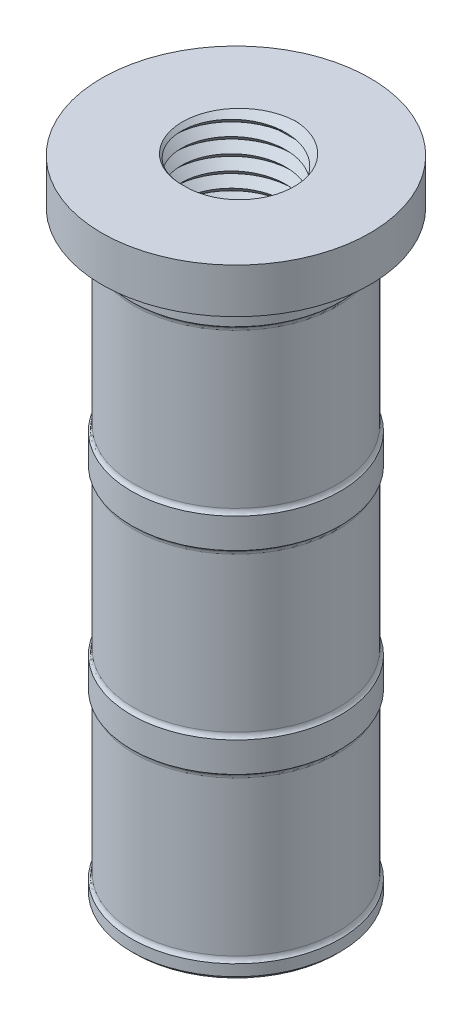
SolidWorks part; units mm, degrees
material "6061-T6 (SS)"
ref_plane "Front Plane" through (0, 0, 0) normal (0, 0, 1) x (1, 0, 0)
ref_plane "Top Plane" through (0, 0, 0) normal (0, 1, 0) x (1, 0, 0)
ref_plane "Right Plane" through (0, 0, 0) normal (1, 0, 0) x (0, 0, -1)
sketch "Sketch1" plane through (0, 0, 0) normal (1, 0, 0) x (0, 0, -1)
  line L0 (0, 48.6222) -> (0, -44.1778) construction
  line L1 (-7, 20.5) -> (-7, 18.5)
  line L2 (-6.825, -18.5) -> (-7, -18.5)
  line L3 (-7, 20.5) -> (-9, 20.5)
  line L4 (-9, 23.5) -> (-4, 23.5)
  line L5 (4.95, 0) -> (-4.95, 0) construction
  line L6 (-7, -18.5) -> (-7, -19.5)
  line L7 (-9, 23.5) -> (-9, 20.5)
  line L8 (-7, 18.5) -> (-6.825, 18.5)
  line L9 (-6.825, 18.5) -> (-6.825, 7.5)
  line L10 (-7, -19.5) -> (-4, -19.5)
  line L11 (-4, -19.5) -> (-4, 23.5)
  line L12 (-6.825, 7.5) -> (-7, 7.5)
  line L13 (-7, 7.5) -> (-7, 5.5)
  line L14 (-7, 5.5) -> (-6.825, 5.5)
  line L15 (-6.825, 5.5) -> (-6.825, -5.5)
  line L16 (-6.825, -5.5) -> (-7, -5.5)
  line L17 (-7, -5.5) -> (-7, -7.5)
  line L18 (-7, -7.5) -> (-6.825, -7.5)
  line L19 (-6.825, -7.5) -> (-6.825, -18.5)
  point P11 (-7, 19.5)
  dimension "D1" = 1
  dimension "D2" = 11
  dimension "D3" = 3
  dimension "D4" = 2
  dimension "D5" = 2
  dimension "D6" = 4
  dimension "D7" = 7
  dimension "D8" = 11
  dimension "D9" = 23.5
  dimension "D10" = 5
  dimension "D11" = 2
  dimension "D12" = 11
  dimension "D13" = 7
  dimension "D14" = 6.825
  dimension "D15" = 7
  dimension "D16" = 7
  dimension "D17" = 6.825
  dimension "D18" = 6.825
revolve "Revolve2" add sketch "Sketch1" angle 360 about L0
sketch "Sketch2" plane through (0, 0, 0) normal (1, 0, 0) x (0, 0, -1)
  line L0 (-4.0008, 23.5) -> (-4.0008, 24)
  line L3 (-4.0008, 24) -> (-3.5008, 23.5)
  line L4 (-3.5008, 23.5) -> (-4.0008, 23)
  line L5 (-4.0008, 23) -> (-4.0008, 23.5)
  line L6 (9.9, 0) -> (-9.9, 0) construction
  dimension "D1" = 0.5
  dimension "D2" = 0.5
  dimension "D3" = 0.5
  dimension "D4" = 24
ref_plane "Plane1" through (0, 23.5, 0) normal (0, 1, 0) x (1, 0, 0)
sketch "Sketch3" plane through (0, 23.5, 0) normal (0, 1, 0) x (1, 0, 0)
  circle A0 centre (0, 0) radius 4
curve "Helix/Spiral1" pitch 1 height 29 radius 4 centre (0, 23.5, 0) axis (0, -1, 0) start towards (0, 0, -1)
sweep "Sweep1" add profiles "Sketch2" path "Helix/Spiral1"
sketch "Sketch4" plane through (0, 0, 0) normal (0, 0, 1) x (1, 0, 0)
  line L0 (9, 23.5) -> (-9, 23.5) construction
  line L1 (-7.2679, 23.5) -> (7.699, 23.5)
  line L2 (-7.2679, 23.5) -> (-7.2679, 24.6372)
  line L3 (-7.2679, 24.6372) -> (7.699, 24.6372)
  line L4 (7.699, 23.5) -> (7.699, 24.6372)
  dimension "D1" = 0
extrude "Cut-Extrude1" cut sketch "Sketch4" against normal through all both and the other way through all
chamfer "Chamfer1" distance 0.25 angle 45 1 edges at (0, -19.5, 7)
sketch "Sketch6" plane through (0, 0, 0) normal (0, 0, 1) x (1, 0, 0)
  line L0 (0, 26.1079) -> (0, 11.6967) construction
  line L1 (0, -9.9) -> (0, 9.9) construction
sketch "Sketch8" plane through (0, -19.5, 0) normal (0, -1, 0) x (1, 0, 0)
  circle A0 centre (0, 0) radius 5
  dimension "D1" = 10
extrude "Cut-Extrude3" cut sketch "Sketch8" against normal blind 15
fillet "Fillet11" radius 1 1 edges at (0, -4.5, -5)
fillet "Fillet12" radius 0.4 6 edges at (0, -7.5, 6.825) (0, -18.5, 6.825) (0, 5.5, 6.825) (0, -5.5, 6.825) (0, 18.5, 6.825) (0, 7.5, 6.825)
fillet "Fillet13" radius 0.5 1 edges at (0, 20.5, 7)
